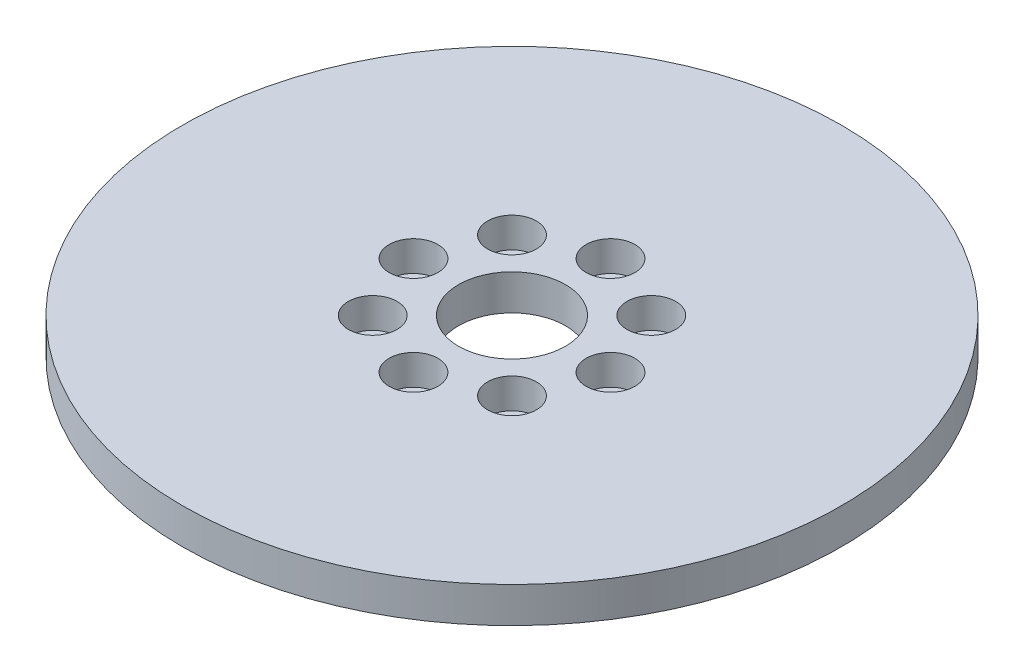
SolidWorks part; units mm, degrees
ref_plane "Front Plane" through (0, 0, 0) normal (0, 0, 1) x (1, 0, 0)
ref_plane "Top Plane" through (0, 0, 0) normal (0, 1, 0) x (1, 0, 0)
ref_plane "Right Plane" through (0, 0, 0) normal (1, 0, 0) x (0, 0, -1)
sketch "Sketch1" plane through (0, 0, 0) normal (0, 1, 0) x (1, 0, 0)
  circle A0 centre (0, 0) radius 92.5
  dimension "FLANGE_OD" = 185
extrude "Boss-Extrude1" add sketch "Sketch1" along normal blind 10
sketch "Sketch2" plane through (0, 0, 0) normal (0, 1, 0) x (1, 0, 0)
  circle A0 centre (0, 0) radius 15
  dimension "BORE_D" = 30
extrude "Cut-Extrude1" cut sketch "Sketch2" along normal through all
sketch "Sketch3" plane through (0, 10, 0) normal (0, 1, 0) x (1, 0, 0)
  circle A0 centre (0, 0) radius 27.649 construction
  circle A1 centre (-27.649, 0) radius 6.837
  dimension "BOLT_D" = 13.674
  dimension "BOLT_PCD" = 55.298
extrude "Cut-Extrude2" cut sketch "Sketch3" against normal blind 8.467
pattern_circular "CirPattern1" count 8 over 360 about axis through (0, 0, 0) along (0, 1, 0) of "Cut-Extrude2"
